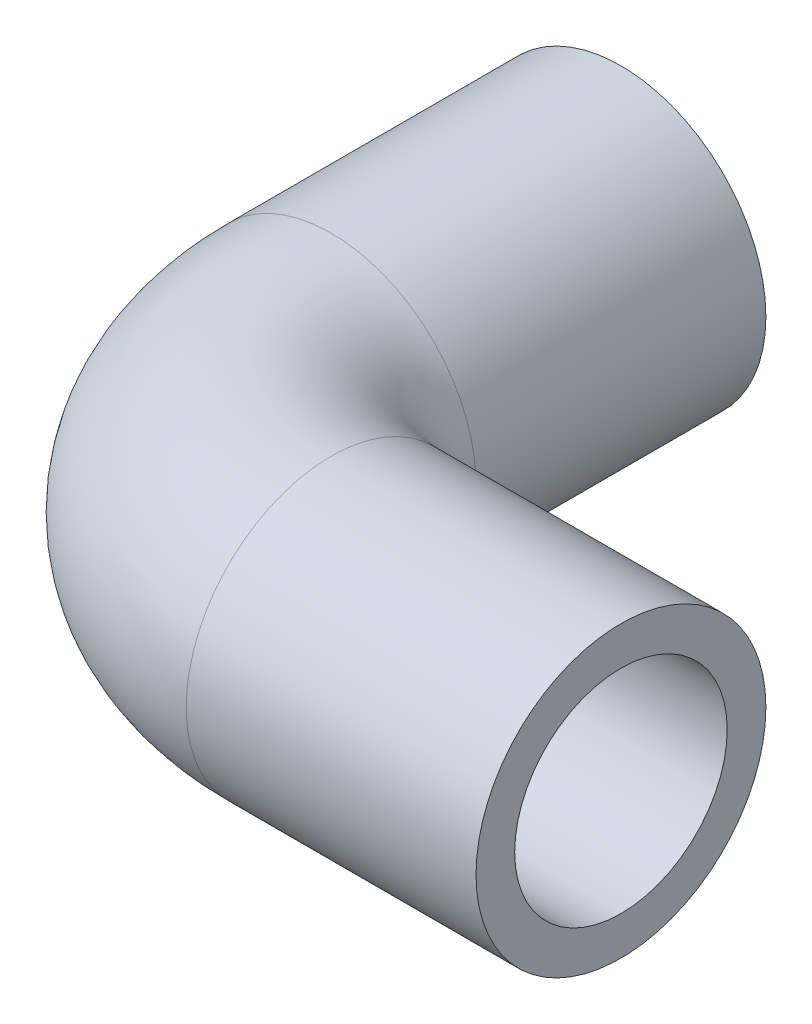
SolidWorks part; units mm, degrees
material "Plain Carbon Steel"
ref_plane "Front Plane" through (0, 0, 0) normal (0, 0, 1) x (1, 0, 0)
ref_plane "Top Plane" through (0, 0, 0) normal (0, 1, 0) x (1, 0, 0)
ref_plane "Right Plane" through (0, 0, 0) normal (1, 0, 0) x (0, 0, -1)
sketch "Sketch1" plane through (0, 0, 0) normal (0, 1, 0) x (1, 0, 0)
  line L0 (0, 0) -> (-75, 0)
  line L1 (-125, 50) -> (-125, 125)
  arc A0 (-75, 0) -> (-125, 50) centre (-75, 50) cw
  dimension "D1" = 75
  dimension "D2" = 75
  dimension "D3" = 50
  dimension "D4" = 50
sweep "Sweep1" add path "Sketch1" circular profile diameter 75 parameters "D3"=75
shell "Shell1" thickness 10 removed face at (0, 0, -37.5)
sketch "Sketch6" plane through (0, 0, -125) normal (0, 0, -1) x (-1, 0, 0)
  line L0 (125, 27.5) -> (125, 37.5)
  circle A0 centre (125, 0) radius 27.5
  circle A1 centre (125, 0) radius 37.5 construction
  dimension "D1" = 10
extrude "Cut-Extrude1" cut sketch "Sketch6" against normal up to next contours A0 region at (-125, 0, -125)
